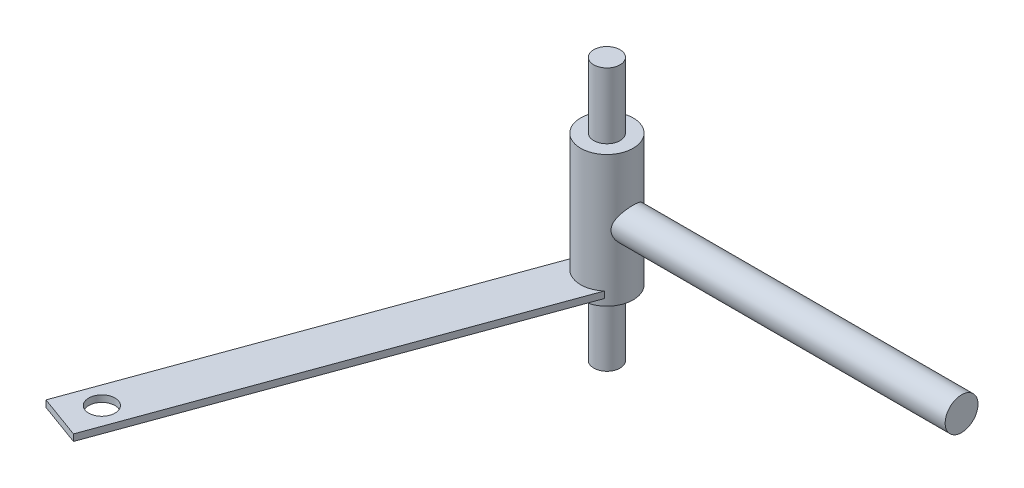
SolidWorks part; units mm, degrees
ref_plane "Front Plane" through (0, 0, 0) normal (0, 0, 1) x (1, 0, 0)
ref_plane "Top Plane" through (0, 0, 0) normal (0, 1, 0) x (1, 0, 0)
ref_plane "Right Plane" through (0, 0, 0) normal (1, 0, 0) x (0, 0, -1)
sketch "Sketch1" plane through (0, 0, 0) normal (0, 1, 0) x (1, 0, 0)
  circle A0 centre (0, 0) radius 4
  dimension "D1" = 8
extrude "Boss-Extrude1" add sketch "Sketch1" along normal mid plane 80
ref_axis "Axis1" through (0, 40, 0) along (0, -1, 0)
ref_plane "Plane1" through (0, 0, 0) normal (-0.342, 0, 0.9397) x (0, -1, 0)
sketch "Sketch3" plane through (0, 0, 0) normal (0, 1, 0) x (1, 0, 0)
  circle A0 centre (0, 0) radius 8
  dimension "D1" = 16
extrude "Boss-Extrude2" add sketch "Sketch3" along normal mid plane 40
sketch "Sketch4" plane through (0, 0, 0) normal (1, 0, 0) x (0, 0, -1)
  circle A0 centre (0, 0) radius 5
  dimension "D1" = 10
extrude "Boss-Extrude3" add sketch "Sketch4" along normal blind 108
sketch "Sketch5" plane through (0, 0, 0) normal (-0.342, 0, 0.9397) x (0.9397, 0, 0.342)
  line L0 (-8, -20) -> (8, -20) construction
  line L5 (-7, -16) -> (7, -16)
  line L6 (-7, -16) -> (-7, -18)
  line L7 (-7, -18) -> (7, -18)
  line L8 (7, -16) -> (7, -18)
  line L9 (-7, -16) -> (7, -18) construction
  line L10 (-7, -18) -> (7, -16) construction
  point P0 (0, -17)
  dimension "D1" = 14
  dimension "D2" = 2
  dimension "D3" = 2
extrude "Boss-Extrude4" add sketch "Sketch5" along normal blind 130
sketch "Sketch6" plane through (0, -16, 0) normal (0, 1, 0) x (1, 0, 0)
  line L0 (-37.8848, -124.5542) -> (-51.0405, -119.7659) construction
  line L1 (-37.8848, -124.5542) -> (5.2532, -6.0336) construction
  circle A0 centre (-41.0424, -112.7631) radius 4
  dimension "D1" = 8
  dimension "D2" = 10
  dimension "D3" = 7
extrude "Cut-Extrude1" cut sketch "Sketch6" against normal up to next
